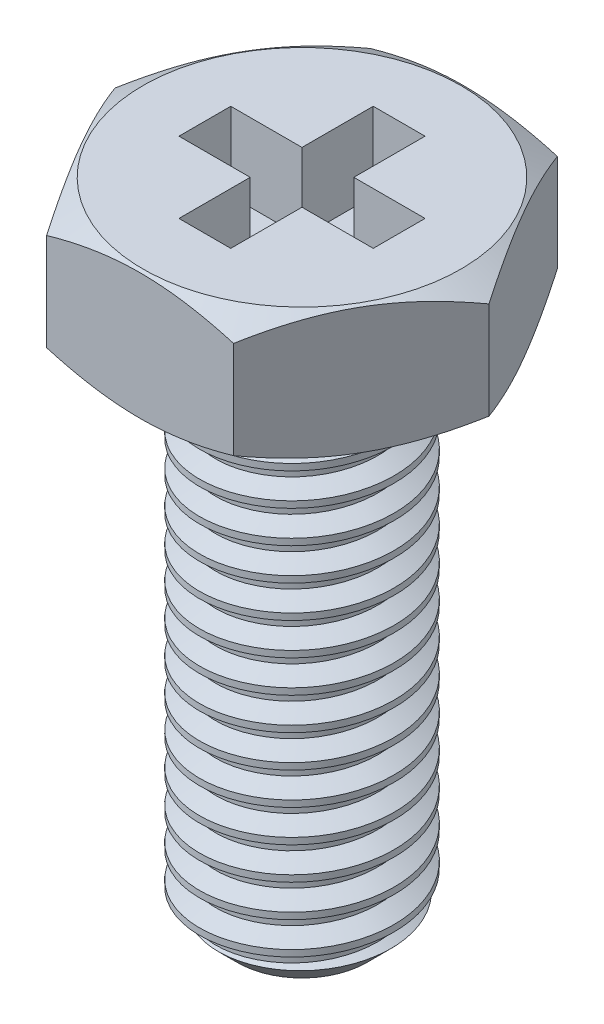
SolidWorks part; units mm, degrees
ref_plane "前基準面" through (0, 0, 0) normal (0, 0, 1) x (1, 0, 0)
ref_plane "上基準面" through (0, 0, 0) normal (0, 1, 0) x (1, 0, 0)
ref_plane "右基準面" through (0, 0, 0) normal (1, 0, 0) x (0, 0, -1)
sketch "草圖9" plane through (0, 0, 0) normal (0, 1, 0) x (1, 0, 0)
  line L1 (2.8868, 0) -> (1.4434, 2.5)
  line L2 (1.4434, 2.5) -> (-1.4434, 2.5)
  line L3 (-1.4434, 2.5) -> (-2.8868, 0)
  line L4 (-2.8868, 0) -> (-1.4434, -2.5)
  line L5 (-1.4434, -2.5) -> (1.4434, -2.5)
  line L6 (1.4434, -2.5) -> (2.8868, 0)
  circle A0 centre (0, 0) radius 2.5 construction
  dimension "D1" = 5
extrude "填料-伸長3" add sketch "草圖9" along normal blind 2
sketch "草圖10" plane through (0, 0, 0) normal (0, 0, 1) x (1, 0, 0)
  line L0 (2.4548, 2) -> (2.8868, 1.7506)
  line L1 (1.4434, 2) -> (2.8868, 2) construction
  line L2 (2.8868, 2) -> (2.8868, 0) construction
  line L3 (2.8868, 1.7506) -> (2.8868, 2)
  line L4 (2.8868, 2) -> (2.4548, 2)
  line L5 (2.8868, 1) -> (-4.4604, 1) construction
  line L6 (2.8868, 0) -> (2.4548, 0)
  line L7 (2.8868, 0.2494) -> (2.8868, 0)
  line L8 (2.4548, 0) -> (2.8868, 0.2494)
  line L9 (0, 0) -> (0, 2.7352) construction
  dimension "D1" = 30
revolve "除料-旋轉3" cut sketch "草圖10" angle 360 about L9
sketch "草圖11" plane through (0, 0, 0) normal (0, -1, 0) x (1, 0, 0)
  circle A0 centre (0, 0) radius 1.5
  dimension "D1" = 3
extrude "填料-伸長4" add sketch "草圖11" along normal blind 8
chamfer "導角3" distance 0.5 angle 45 1 edges at (0, -8, -1.5)
sketch "草圖13" plane through (0, -8, 0) normal (0, -1, 0) x (1, 0, 0)
  circle A0 centre (0, 0) radius 1.5 construction
  circle A1 centre (0, 0) radius 1.5
curve "螺旋曲線/渦捲線2" pitch 0.5 height 7.5 radius 1.5 centre (0, -8, 0) axis (0, 1, 0) start towards (1, 0, 0)
sketch "草圖14" plane through (0, 0, 0) normal (0, 0, 1) x (1, 0, 0)
  line L0 (1.25, -8.0557) -> (1.25, -7.9443)
  line L1 (1.25, -7.9443) -> (1.5, -7.8)
  line L2 (1.5, -7.8) -> (1.5, -8.2)
  line L3 (1.5, -8) -> (1.25, -8) construction
  line L4 (1.25, -8.0557) -> (1.5, -8.2)
  spline S0 degree 3 poles (1.5, -8) (1.5, -7.9896) (1.4219, -7.9687) (1.0883, -7.9375) (0.589, -7.9062) (0, -7.875) (-0.589, -7.8437) (-1.0883, -7.8125) (-1.4219, -7.7812) (-1.5391, -7.75) (-1.4219, -7.7187) (-1.0883, -7.6875) (-0.589, -7.6562) (0, -7.625) (0.589, -7.5937) (1.0883, -7.5625) (1.4219, -7.5312) (1.5391, -7.5) (1.4219, -7.4687) (1.0883, -7.4375) (0.589, -7.4062) (0, -7.375) (-0.589, -7.3437) (-1.0883, -7.3125) (-1.4219, -7.2812) (-1.5391, -7.25) (-1.4219, -7.2187) (-1.0883, -7.1875) (-0.589, -7.1562) (0, -7.125) (0.589, -7.0938) (1.0883, -7.0625) (1.4219, -7.0312) (1.5391, -7) (1.4219, -6.9688) (1.0883, -6.9375) (0.589, -6.9062) (0, -6.875) (-0.589, -6.8438) (-1.0883, -6.8125) (-1.4219, -6.7812) (-1.5391, -6.75) (-1.4219, -6.7188) (-1.0883, -6.6875) (-0.589, -6.6562) (0, -6.625) (0.589, -6.5937) (1.0883, -6.5625) (1.4219, -6.5313) (1.5391, -6.5) (1.4219, -6.4688) (1.0883, -6.4375) (0.589, -6.4062) (0, -6.375) (-0.589, -6.3438) (-1.0883, -6.3125) (-1.4219, -6.2812) (-1.5391, -6.25) (-1.4219, -6.2188) (-1.0883, -6.1875) (-0.589, -6.1562) (0, -6.125) (0.589, -6.0938) (1.0883, -6.0625) (1.4219, -6.0312) (1.5391, -6) (1.4219, -5.9687) (1.0883, -5.9375) (0.589, -5.9062) (0, -5.875) (-0.589, -5.8437) (-1.0883, -5.8125) (-1.4219, -5.7812) (-1.5391, -5.75) (-1.4219, -5.7187) (-1.0883, -5.6875) (-0.589, -5.6562) (0, -5.625) (0.589, -5.5937) (1.0883, -5.5625) (1.4219, -5.5312) (1.5391, -5.5) (1.4219, -5.4687) (1.0883, -5.4375) (0.589, -5.4062) (0, -5.375) (-0.589, -5.3437) (-1.0883, -5.3125) (-1.4219, -5.2812) (-1.5391, -5.25) (-1.4219, -5.2187) (-1.0883, -5.1875) (-0.589, -5.1562) (0, -5.125) (0.589, -5.0937) (1.0883, -5.0625) (1.4219, -5.0312) (1.5391, -5) (1.4219, -4.9687) (1.0883, -4.9375) (0.589, -4.9062) (0, -4.875) (-0.589, -4.8437) (-1.0883, -4.8125) (-1.4219, -4.7812) (-1.5391, -4.75) (-1.4219, -4.7187) (-1.0883, -4.6875) (-0.589, -4.6562) (0, -4.625) (0.589, -4.5937) (1.0883, -4.5625) (1.4219, -4.5312) (1.5391, -4.5) (1.4219, -4.4687) (1.0883, -4.4375) (0.589, -4.4062) (0, -4.375) (-0.589, -4.3437) (-1.0883, -4.3125) (-1.4219, -4.2812) (-1.5391, -4.25) (-1.4219, -4.2187) (-1.0883, -4.1875) (-0.589, -4.1562) (0, -4.125) (0.589, -4.0937) (1.0883, -4.0625) (1.4219, -4.0312) (1.5391, -4) (1.4219, -3.9687) (1.0883, -3.9375) (0.589, -3.9062) (0, -3.875) (-0.589, -3.8437) (-1.0883, -3.8125) (-1.4219, -3.7812) (-1.5391, -3.75) (-1.4219, -3.7187) (-1.0883, -3.6875) (-0.589, -3.6562) (0, -3.625) (0.589, -3.5937) (1.0883, -3.5625) (1.4219, -3.5312) (1.5391, -3.5) (1.4219, -3.4687) (1.0883, -3.4375) (0.589, -3.4062) (0, -3.375) (-0.589, -3.3437) (-1.0883, -3.3125) (-1.4219, -3.2812) (-1.5391, -3.25) (-1.4219, -3.2187) (-1.0883, -3.1875) (-0.589, -3.1562) (0, -3.125) (0.589, -3.0937) (1.0883, -3.0625) (1.4219, -3.0312) (1.5391, -3) (1.4219, -2.9687) (1.0883, -2.9375) (0.589, -2.9062) (0, -2.875) (-0.589, -2.8437) (-1.0883, -2.8125) (-1.4219, -2.7812) (-1.5391, -2.75) (-1.4219, -2.7187) (-1.0883, -2.6875) (-0.589, -2.6562) (0, -2.625) (0.589, -2.5937) (1.0883, -2.5625) (1.4219, -2.5312) (1.5391, -2.5) (1.4219, -2.4687) (1.0883, -2.4375) (0.589, -2.4062) (0, -2.375) (-0.589, -2.3437) (-1.0883, -2.3125) (-1.4219, -2.2812) (-1.5391, -2.25) (-1.4219, -2.2187) (-1.0883, -2.1875) (-0.589, -2.1562) (0, -2.125) (0.589, -2.0937) (1.0883, -2.0625) (1.4219, -2.0312) (1.5391, -2) (1.4219, -1.9687) (1.0883, -1.9375) (0.589, -1.9062) (0, -1.875) (-0.589, -1.8437) (-1.0883, -1.8125) (-1.4219, -1.7812) (-1.5391, -1.75) (-1.4219, -1.7187) (-1.0883, -1.6875) (-0.589, -1.6562) (0, -1.625) (0.589, -1.5937) (1.0883, -1.5625) (1.4219, -1.5312) (1.5391, -1.5) (1.4219, -1.4687) (1.0883, -1.4375) (0.589, -1.4062) (0, -1.375) (-0.589, -1.3437) (-1.0883, -1.3125) (-1.4219, -1.2812) (-1.5391, -1.25) (-1.4219, -1.2187) (-1.0883, -1.1875) (-0.589, -1.1562) (0, -1.125) (0.589, -1.0937) (1.0883, -1.0625) (1.4219, -1.0313) (1.5391, -1) (1.4219, -0.9688) (1.0883, -0.9375) (0.589, -0.9063) (0, -0.875) (-0.589, -0.8438) (-1.0883, -0.8125) (-1.4219, -0.7813) (-1.5391, -0.75) (-1.4219, -0.7188) (-1.0883, -0.6875) (-0.589, -0.6563) (0, -0.625) (0.589, -0.5938) (1.0883, -0.5625) (1.4219, -0.5313) (1.5, -0.5104) (1.5, -0.5) knots 0 0 0 0 0.004167 0.008333 0.0125 0.016667 0.020833 0.025 0.029167 0.033333 0.0375 0.041667 0.045833 0.05 0.054167 0.058333 0.0625 0.066667 0.070833 0.075 0.079167 0.083333 0.0875 0.091667 0.095833 0.1 0.104167 0.108333 0.1125 0.116667 0.120833 0.125 0.129167 0.133333 0.1375 0.141667 0.145833 0.15 0.154167 0.158333 0.1625 0.166667 0.170833 0.175 0.179167 0.183333 0.1875 0.191667 0.195833 0.2 0.204167 0.208333 0.2125 0.216667 0.220833 0.225 0.229167 0.233333 0.2375 0.241667 0.245833 0.25 0.254167 0.258333 0.2625 0.266667 0.270833 0.275 0.279167 0.283333 0.2875 0.291667 0.295833 0.3 0.304167 0.308333 0.3125 0.316667 0.320833 0.325 0.329167 0.333333 0.3375 0.341667 0.345833 0.35 0.354167 0.358333 0.3625 0.366667 0.370833 0.375 0.379167 0.383333 0.3875 0.391667 0.395833 0.4 0.404167 0.408333 0.4125 0.416667 0.420833 0.425 0.429167 0.433333 0.4375 0.441667 0.445833 0.45 0.454167 0.458333 0.4625 0.466667 0.470833 0.475 0.479167 0.483333 0.4875 0.491667 0.495833 0.5 0.504167 0.508333 0.5125 0.516667 0.520833 0.525 0.529167 0.533333 0.5375 0.541667 0.545833 0.55 0.554167 0.558333 0.5625 0.566667 0.570833 0.575 0.579167 0.583333 0.5875 0.591667 0.595833 0.6 0.604167 0.608333 0.6125 0.616667 0.620833 0.625 0.629167 0.633333 0.6375 0.641667 0.645833 0.65 0.654167 0.658333 0.6625 0.666667 0.670833 0.675 0.679167 0.683333 0.6875 0.691667 0.695833 0.7 0.704167 0.708333 0.7125 0.716667 0.720833 0.725 0.729167 0.733333 0.7375 0.741667 0.745833 0.75 0.754167 0.758333 0.7625 0.766667 0.770833 0.775 0.779167 0.783333 0.7875 0.791667 0.795833 0.8 0.804167 0.808333 0.8125 0.816667 0.820833 0.825 0.829167 0.833333 0.8375 0.841667 0.845833 0.85 0.854167 0.858333 0.8625 0.866667 0.870833 0.875 0.879167 0.883333 0.8875 0.891667 0.895833 0.9 0.904167 0.908333 0.9125 0.916667 0.920833 0.925 0.929167 0.933333 0.9375 0.941667 0.945833 0.95 0.954167 0.958333 0.9625 0.966667 0.970833 0.975 0.979167 0.983333 0.9875 0.991667 0.995833 1 1 1 1 construction
  point P8 (1.25, -8)
  point P9 (1.5, -7.8)
  dimension "D1" = 0.25
  dimension "D2" = 0.2
  dimension "D3" = 30
sweep "除料-掃出5" cut profiles "草圖14" path "螺旋曲線/渦捲線2" align with end faces yes
sketch "草圖15" plane through (0, 2, 0) normal (0, 1, 0) x (1, 0, 0)
  line L0 (0, 0) -> (2.5721, 0) construction
  line L1 (0, 0) -> (0, 2.6587) construction
  line L2 (0.4, 0.4) -> (1.5, 0.4)
  line L3 (1.5, 0.4) -> (1.5, 0)
  line L4 (0.4, 0.4) -> (0.4, 1.5)
  line L5 (0.4, 1.5) -> (0, 1.5)
  line L6 (0.4, -1.5) -> (0, -1.5)
  line L7 (0.4, -0.4) -> (0.4, -1.5)
  line L8 (0.4, -0.4) -> (1.5, -0.4)
  line L9 (1.5, -0.4) -> (1.5, 0)
  line L10 (-1.5, -0.4) -> (-1.5, 0)
  line L11 (-0.4, -0.4) -> (-1.5, -0.4)
  line L12 (-0.4, -0.4) -> (-0.4, -1.5)
  line L13 (-0.4, -1.5) -> (0, -1.5)
  line L14 (-0.4, 1.5) -> (0, 1.5)
  line L15 (-0.4, 0.4) -> (-0.4, 1.5)
  line L16 (-0.4, 0.4) -> (-1.5, 0.4)
  line L17 (-1.5, 0.4) -> (-1.5, 0)
  point P27 (0, 0)
  dimension "D1" = 0.4
  dimension "D2" = 0.4
  dimension "D3" = 1.5
  dimension "D4" = 1.5
  dimension "D5" = 4
extrude "除料-伸長1" cut sketch "草圖15" against normal blind 1.2
